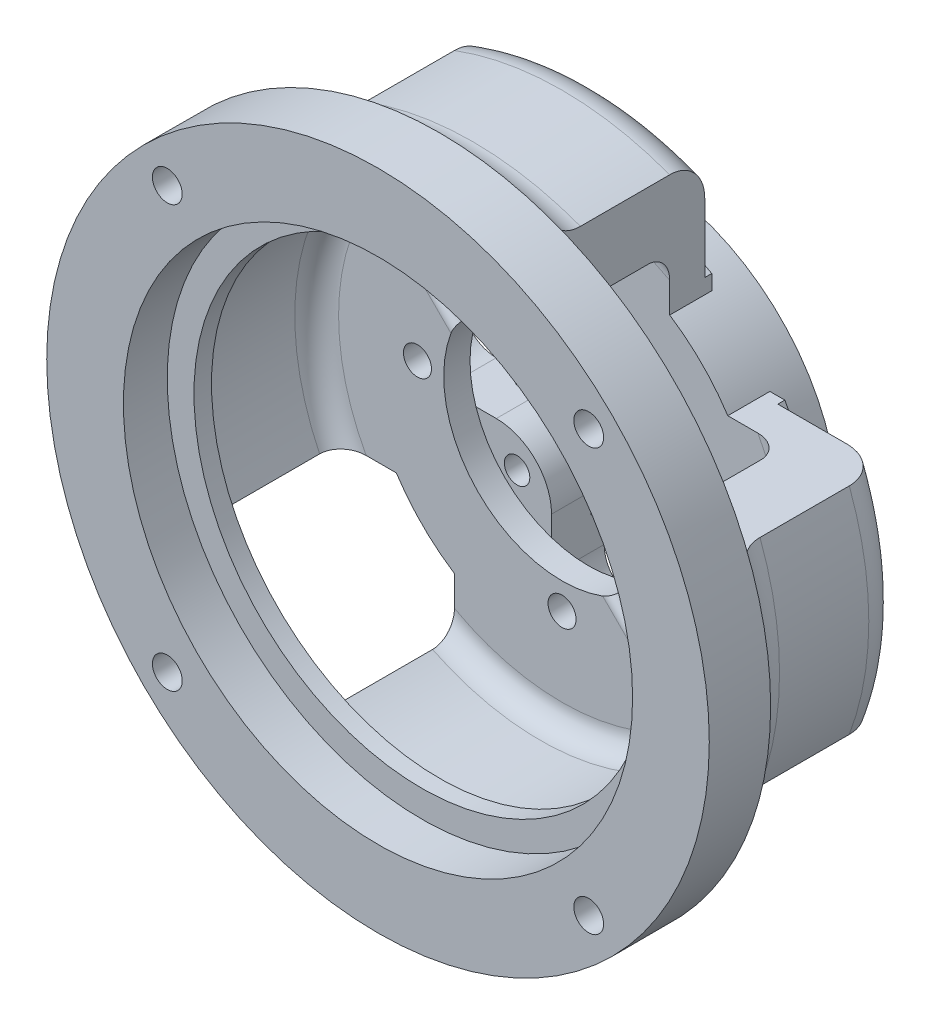
SolidWorks part; units mm, degrees
ref_plane "前视基准面" through (0, 0, 0) normal (0, 0, 1) x (1, 0, 0)
ref_plane "上视基准面" through (0, 0, 0) normal (0, 1, 0) x (1, 0, 0)
ref_plane "右视基准面" through (0, 0, 0) normal (1, 0, 0) x (0, 0, -1)
sketch "草图1" plane through (0, 0, 0) normal (0, 1, 0) x (1, 0, 0)
  line L0 (37.8, 30.0102) -> (0, 30.0102)
  line L1 (0, 30.0102) -> (0, 24.0102)
  line L2 (0, 24.0102) -> (37.8, 24.0102)
  line L3 (37.8, 24.0102) -> (37.8, 30.0102)
  line L4 (0, 30.0102) -> (0, 24.0102) construction
revolve "旋转1" add sketch "草图1" angle 360 about L4
sketch "草图2" plane through (0, 0, -30.0102) normal (0, 0, -1) x (-1, 0, 0)
  line L24 (-22.4395, -21.2666) -> (-25.6438, -21.2666)
  line L25 (-25.6438, -21.2666) -> (-27.2459, -24.0416)
  line L26 (-20.8373, -24.0416) -> (-22.4395, -21.2666)
  line L27 (-22.4395, -26.8166) -> (-20.8373, -24.0416)
  line L28 (-25.6438, -26.8166) -> (-22.4395, -26.8166)
  line L29 (-27.2459, -24.0416) -> (-25.6438, -26.8166)
  line L75 (-20.8373, -24.0416) -> (-27.2459, -24.0416) construction
  line L76 (-22.4395, -21.2666) -> (-25.6438, -26.8166) construction
  line L77 (-25.6438, -21.2666) -> (-22.4395, -26.8166) construction
  line L78 (0, 0) -> (-24.0416, -24.0416) construction
  line L169 (0, 0) -> (0, -46.6036) construction
  line L170 (-24.0416, 27.2459) -> (-26.8166, 25.6438)
  line L171 (-21.2666, 25.6438) -> (-24.0416, 27.2459)
  line L172 (-21.2666, 22.4395) -> (-21.2666, 25.6438)
  line L173 (-24.0416, 20.8373) -> (-21.2666, 22.4395)
  line L174 (-26.8166, 22.4395) -> (-24.0416, 20.8373)
  line L175 (-26.8166, 25.6438) -> (-26.8166, 22.4395)
  line L176 (27.2459, 24.0416) -> (25.6438, 26.8166)
  line L177 (25.6438, 21.2666) -> (27.2459, 24.0416)
  line L178 (22.4395, 21.2666) -> (25.6438, 21.2666)
  line L179 (20.8373, 24.0416) -> (22.4395, 21.2666)
  line L180 (22.4395, 26.8166) -> (20.8373, 24.0416)
  line L181 (25.6438, 26.8166) -> (22.4395, 26.8166)
  line L182 (24.0416, -27.2459) -> (26.8166, -25.6438)
  line L183 (21.2666, -25.6438) -> (24.0416, -27.2459)
  line L184 (21.2666, -22.4395) -> (21.2666, -25.6438)
  line L185 (24.0416, -20.8373) -> (21.2666, -22.4395)
  line L186 (26.8166, -22.4395) -> (24.0416, -20.8373)
  line L187 (26.8166, -25.6438) -> (26.8166, -22.4395)
  point P24 (0, 0)
  point P41 (0, 0)
  point P74 (0, 0)
  point P165 (0, 0)
  dimension "D1" = 4
  dimension "D2" = 45
extrude "切除-拉伸1" cut sketch "草图2" against normal blind 2.5
hole_wizard "M48 六角头螺栓的柱形沉头孔1" positions "草图15" profile "草图14" counterbore size "M48" standard "ANSI Metric" end condition through all
sketch "草图15" plane through (0, 0, -24.0102) normal (0, 0, 1) x (1, 0, 0)
  point P0 (0, 0)
sketch "草图14" plane through (0, 0, -24.0102) normal (1, 0, 0) x (0, -1, 0)
  line L0 (0, 0) -> (0, 6)
  line L1 (0, 6) -> (26, 6)
  line L3 (26, 6) -> (26, 4)
  line L4 (26, 4) -> (29.05, 4)
  line L5 (29.05, 4) -> (29.05, 0)
  line L7 (29.05, 0) -> (0, 0)
  line L11 (0, -6.35) -> (0, 107.95) construction
  dimension "通孔孔直径" = 52
  dimension "通孔孔深度" = 6
  dimension "柱形沉头孔直径" = 58.1
  dimension "柱形沉头孔深度" = 4
sketch "草图17" plane through (0, 0, -30.0102) normal (0, 0, -1) x (-1, 0, 0)
  line L0 (0, 0) -> (-24.0416, -24.0416) construction
  line L1 (0, 0) -> (0, -49.8277) construction
  circle A0 centre (-24.0416, -24.0416) radius 1.7
  circle A16 centre (-24.0416, 24.0416) radius 1.7
  circle A17 centre (24.0416, 24.0416) radius 1.7
  circle A18 centre (24.0416, -24.0416) radius 1.7
  point P13 (0, 0)
  point P16 (0, 0)
  point P27 (0, 0)
  dimension "D2" = 45
  dimension "D1" = 4
extrude "切除-拉伸2" cut sketch "草图17" against normal blind 6 and the other way through all
sketch "草图18" plane through (0, 0, -30.0102) normal (0, 0, -1) x (-1, 0, 0)
  circle A1 centre (0, 0) radius 35
extrude "凸台-拉伸1" add sketch "草图18" along normal blind 23
sketch "草图19" plane through (0, 0, -30.0102) normal (0, 0, 1) x (1, 0, 0)
  circle A0 centre (0, 0) radius 28
  dimension "D1" = 56
extrude "切除-拉伸3" cut sketch "草图19" against normal blind 14
sketch "草图20" plane through (0, 0, -53.0102) normal (0, 0, -1) x (-1, 0, 0)
  line L0 (0, 0) -> (0, -35) construction
  line L1 (0, 0) -> (-19.0624, -29.3535) construction
  line L2 (0, 0) -> (-29.3535, -19.0624) construction
  line L13 (-18.912, -12.2816) -> (-32.7744, -12.2816)
  line L14 (-12.2816, -32.7744) -> (-12.2816, -18.912) construction
  line L15 (-18.912, -12.2816) -> (-32.7744, -12.2816) construction
  line L16 (-12.2816, 18.912) -> (-12.2816, 32.7744)
  line L17 (-12.2816, -18.912) -> (-12.2816, -32.7744)
  line L18 (-18.912, 12.2816) -> (-32.7744, 12.2816)
  line L19 (18.912, 12.2816) -> (32.7744, 12.2816)
  line L20 (12.2816, 18.912) -> (12.2816, 32.7744)
  line L21 (12.2816, -18.912) -> (12.2816, -32.7744)
  line L22 (18.912, -12.2816) -> (32.7744, -12.2816)
  circle A0 centre (0, 0) radius 35 construction
  arc A1 (-18.912, -12.2816) -> (-12.2816, -18.912) centre (0, 0) ccw
  arc A2 (-29.3535, -19.0624) -> (-19.0624, -29.3535) centre (0, 0) ccw
  arc A19 (-12.2816, 18.912) -> (-18.912, 12.2816) centre (0, 0) ccw
  arc A20 (-19.0624, 29.3535) -> (-29.3535, 19.0624) centre (0, 0) ccw
  arc A21 (18.912, 12.2816) -> (12.2816, 18.912) centre (0, 0) ccw
  arc A22 (29.3535, 19.0624) -> (19.0624, 29.3535) centre (0, 0) ccw
  arc A23 (12.2816, -18.912) -> (18.912, -12.2816) centre (0, 0) ccw
  arc A24 (19.0624, -29.3535) -> (29.3535, -19.0624) centre (0, 0) ccw
  circle A25 centre (0, 0) radius 13.5
  dimension "D1" = 4
  dimension "D2" = 57
  dimension "D3" = 33
extrude "切除-拉伸5" cut sketch "草图20" against normal blind 23
sketch "草图21" plane through (0, 0, -53.0102) normal (0, 0, -1) x (-1, 0, 0)
  line L0 (0, 20.5051) -> (0, -20.6353) construction
  line L1 (-24.3457, 0) -> (20.7655, 0) construction
  line L2 (-4.2, 16.5) -> (-4.2, 10.5)
  line L3 (-10.5, 4.2) -> (-16.5, 4.2)
  line L4 (-20.5, 0.2) -> (-20.5, -0.2)
  line L5 (-16.5, -4.2) -> (-10.5, -4.2)
  line L6 (-4.2, -10.5) -> (-4.2, -16.5)
  line L7 (-0.2, -20.5) -> (0.2, -20.5)
  line L8 (4.2, -16.5) -> (4.2, -10.5)
  line L9 (10.5, -4.2) -> (16.5, -4.2)
  line L10 (20.5, -0.2) -> (20.5, 0.2)
  line L11 (16.5, 4.2) -> (10.5, 4.2)
  line L12 (4.2, 10.5) -> (4.2, 16.5)
  line L13 (0.2, 20.5) -> (-0.2, 20.5)
  arc A0 (-0.2, -20.5) -> (-4.2, -16.5) centre (-0.2, -16.5) cw
  arc A1 (0.2, -20.5) -> (4.2, -16.5) centre (0.2, -16.5) ccw
  arc A2 (20.5, -0.2) -> (16.5, -4.2) centre (16.5, -0.2) cw
  arc A3 (20.5, 0.2) -> (16.5, 4.2) centre (16.5, 0.2) ccw
  arc A4 (4.2, 16.5) -> (0.2, 20.5) centre (0.2, 16.5) ccw
  arc A5 (-0.2, 20.5) -> (-4.2, 16.5) centre (-0.2, 16.5) ccw
  arc A6 (-20.5, -0.2) -> (-16.5, -4.2) centre (-16.5, -0.2) ccw
  arc A7 (-20.5, 0.2) -> (-16.5, 4.2) centre (-16.5, 0.2) cw
  arc A8 (-10.5, 4.2) -> (-4.2, 10.5) centre (-10.5, 10.5) ccw
  arc A9 (4.2, 10.5) -> (10.5, 4.2) centre (10.5, 10.5) ccw
  arc A10 (10.5, -4.2) -> (4.2, -10.5) centre (10.5, -10.5) ccw
  arc A11 (-4.2, -10.5) -> (-10.5, -4.2) centre (-10.5, -10.5) ccw
  point P35 (-4.2, 4.2)
  dimension "D13" = 4
  dimension "D14" = 6.3
  dimension "D1" = 4.2
  dimension "D2" = 20.5
  dimension "D3" = 4.2
  dimension "D4" = 4.2
  dimension "D5" = 4.2
  dimension "D6" = 20.5
  dimension "D7" = 4.2
  dimension "D8" = 4.2
  dimension "D9" = 4.2
  dimension "D10" = 4.2
  dimension "D11" = 20.5
  dimension "D12" = 20.5
extrude "切除-拉伸6" cut sketch "草图21" against normal blind 6
sketch "草图22" plane through (0, 0, -47.0102) normal (0, 0, -1) x (-1, 0, 0)
  line L0 (0, 0) -> (-16.5, 0) construction
  line L1 (0, 0) -> (0, 16.5) construction
  line L2 (0, 0) -> (16.5, 0) construction
  line L3 (0, 0) -> (0, -16.5) construction
  circle A0 centre (-16.5, 0) radius 1.6
  circle A1 centre (0, 16.5) radius 1.6
  circle A2 centre (16.5, 0) radius 1.6
  circle A3 centre (0, -16.5) radius 1.6
  point P9 (0, 0)
  point P17 (0, 0)
extrude "切除-拉伸7" cut sketch "草图22" against normal blind 3
sketch "草图24" plane through (0, 0, -47.0102) normal (0, 0, -1) x (-1, 0, 0)
  line L0 (-12.83, -4.2) -> (-10.5, -4.2)
  line L1 (-4.2, -10.5) -> (-4.2, -12.83)
  line L2 (-12.83, 4.2) -> (-10.5, 4.2)
  line L3 (-4.2, 10.5) -> (-4.2, 12.83)
  line L4 (4.2, 12.83) -> (4.2, 10.5)
  line L5 (10.5, 4.2) -> (12.83, 4.2)
  line L6 (12.83, -4.2) -> (10.5, -4.2)
  line L7 (4.2, -10.5) -> (4.2, -12.83)
  line L8 (0, 0) -> (-8.1317, -8.1317) construction
  circle A0 centre (0, 0) radius 13.5
  arc A1 (4.2, -10.5) -> (10.5, -4.2) centre (10.5, -10.5) cw
  arc A2 (10.5, 4.2) -> (4.2, 10.5) centre (10.5, 10.5) cw
  arc A3 (-4.2, 10.5) -> (-10.5, 4.2) centre (-10.5, 10.5) cw
  arc A4 (-4.2, -10.5) -> (-10.5, -4.2) centre (-10.5, -10.5) ccw
  circle A6 centre (-8.1317, -8.1317) radius 1.45
  circle A7 centre (-8.1317, 8.1317) radius 1.45
  circle A8 centre (8.1317, 8.1317) radius 1.45
  circle A9 centre (8.1317, -8.1317) radius 1.45
  point P33 (-4.2, 4.2)
  point P47 (0, 0)
  dimension "D1" = 6.3
extrude "凸台-拉伸2" add sketch "草图24" along normal blind 4.5
sketch "草图25" plane through (0, 0, -53.0102) normal (0, 0, -1) x (-1, 0, 0)
  circle A0 centre (0, 0) radius 24
  circle A1 centre (0, 0) radius 35
extrude "切除-拉伸8" cut sketch "草图25" against normal blind 5
sketch "草图27" plane through (0, 0, -53.0102) normal (0, 0, -1) x (-1, 0, 0)
  circle A0 centre (0, 0) radius 24
  circle A1 centre (0, 0) radius 22.55
extrude "切除-拉伸9" cut sketch "草图27" against normal blind 4.2
sketch "草图29" plane through (0, 0, -53.0102) normal (0, 0, -1) x (-1, 0, 0)
  line L1 (-9.5, 11.5) -> (9.5, 11.5)
  line L2 (-11.5, 9.5) -> (-11.5, -9.5)
  line L3 (-9.5, -11.5) -> (9.5, -11.5)
  line L4 (11.5, 9.5) -> (11.5, -9.5)
  line L5 (-11.5, 11.5) -> (11.5, -11.5) construction
  line L6 (-11.5, -11.5) -> (11.5, 11.5) construction
  arc A0 (11.5, -9.5) -> (9.5, -11.5) centre (9.5, -9.5) cw
  arc A1 (-9.5, -11.5) -> (-11.5, -9.5) centre (-9.5, -9.5) cw
  arc A2 (11.5, 9.5) -> (9.5, 11.5) centre (9.5, 9.5) ccw
  arc A3 (-9.5, 11.5) -> (-11.5, 9.5) centre (-9.5, 9.5) ccw
  point P0 (0, 0)
  dimension "D1" = 2
extrude "切除-拉伸10" cut sketch "草图29" against normal blind 1.5
fillet "圆角1" radius 4 4 edges at (0, 35, -48.0102) (-35, 0, -48.0102) (0, -35, -48.0102) (35, 0, -48.0102)
fillet "圆角2" radius 2.5 4 edges at (28, 0, -44.0102) (0, -28, -44.0102) (-28, 0, -44.0102) (0, 28, -44.0102)
sketch "草图30" plane through (0, 0, -53.0102) normal (0, 0, -1) x (-1, 0, 0)
  line L0 (0, 0) -> (32.3138, -32.3138) construction
ref_plane "基准面1" through (0, 0, 0) normal (0.7071, -0.7071, 0) x (-0.7071, -0.7071, 0)
sketch "草图31" plane through (0, 0, 0) normal (0.7071, -0.7071, 0) x (-0.7071, -0.7071, 0)
  line L0 (4.6884, 44.0102) -> (4.6884, 48.8102) construction
  line L1 (-4.6884, 44.0102) -> (4.6884, 44.0102)
  line L2 (-4.6884, 44.0102) -> (-4.6884, 46.4102)
  line L3 (-4.6884, 46.4102) -> (4.6884, 46.4102)
  line L4 (4.6884, 44.0102) -> (4.6884, 46.4102)
extrude "切除-拉伸11" cut sketch "草图31" against normal through all both and the other way through all
fillet "圆角3" radius 1 8 edges at (15.5895, -8.9591, -44.0102) (15.5895, -8.9591, -46.4102) (8.9591, -15.5895, -44.0102) (8.9591, -15.5895, -46.4102) (-15.5895, 8.9591, -46.4102) (-8.9591, 15.5895, -44.0102) (-8.9591, 15.5895, -46.4102) (-15.5895, 8.9591, -44.0102)
fillet "圆角4" radius 4 4 edges at (0, -35, -30.0102) (35, 0, -30.0102) (0, 35, -30.0102) (-35, 0, -30.0102)
sketch "草图33" plane through (0, 0, -24.0102) normal (0, 0, 1) x (1, 0, 0)
  circle A0 centre (0, 0) radius 37.8
  circle A1 centre (0, 0) radius 29.05
  circle A2 centre (-24.0416, -24.0416) radius 1.7
  circle A3 centre (24.0416, -24.0416) radius 1.7
  circle A4 centre (24.0416, 24.0416) radius 1.7
  circle A5 centre (-24.0416, 24.0416) radius 1.7
extrude "凸台-拉伸3" add sketch "草图33" along normal blind 1
